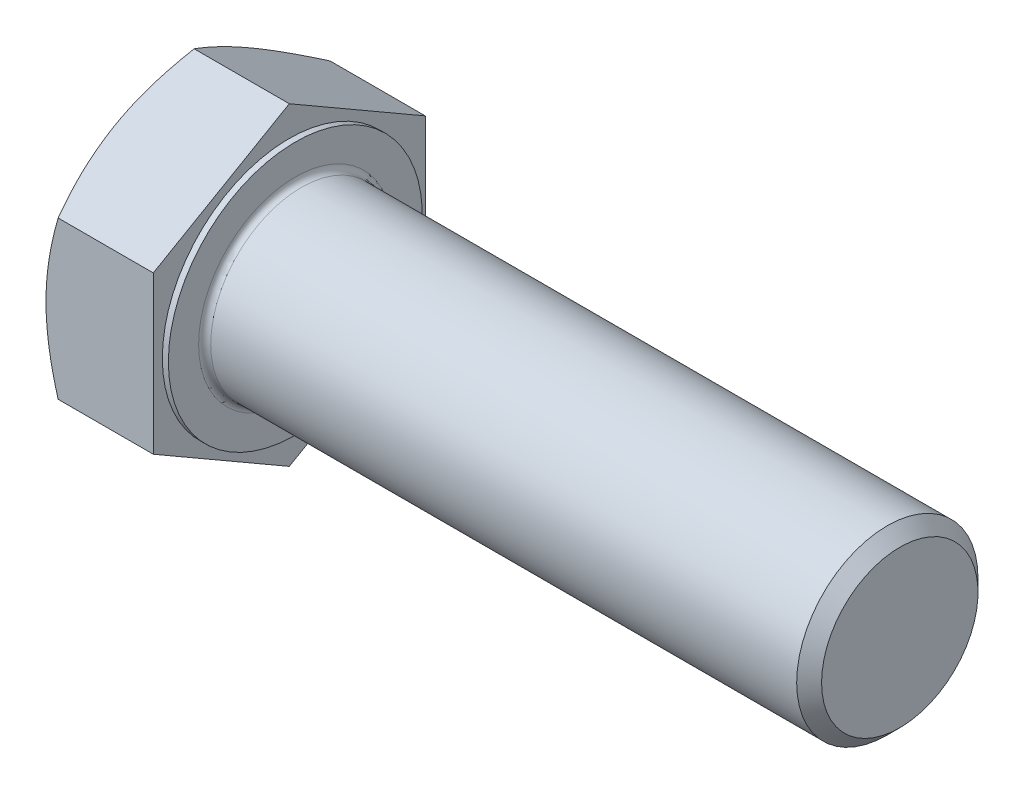
SolidWorks part; units mm, degrees
ref_plane "Front Plane" through (0, 0, 0) normal (0, 0, 1) x (1, 0, 0)
ref_plane "Top Plane" through (0, 0, 0) normal (0, 1, 0) x (1, 0, 0)
ref_plane "Right Plane" through (0, 0, 0) normal (1, 0, 0) x (0, 0, -1)
sketch "BaseHeadSke" plane through (0, 0, 0) normal (1, 0, 0) x (0, 0, -1)
  line L1 (18, 10.3923) -> (0, 20.7846)
  line L2 (0, 20.7846) -> (-18, 10.3923)
  line L3 (-18, 10.3923) -> (-18, -10.3923)
  line L4 (-18, -10.3923) -> (0, -20.7846)
  line L5 (0, -20.7846) -> (18, -10.3923)
  line L6 (18, -10.3923) -> (18, 10.3923)
  circle A0 centre (0, 0) radius 18 construction
extrude "BaseHead" add sketch "BaseHeadSke" along normal blind 15
sketch "BodySke" plane through (0, 0, 0) normal (0, 0, 1) x (1, 0, 0)
  line L0 (0, 0) -> (95, 0)
  line L1 (95, 0) -> (95, 10.352)
  line L2 (95, 10.352) -> (93.352, 12)
  line L3 (93.352, 12) -> (0, 12)
  line L4 (0, 12) -> (0, 0)
  line L5 (15, 10.3923) -> (15, -10.3923) construction
  line L6 (0, 0) -> (159.3976, 0) construction
  line L7 (15, -84.3176) -> (15, 77.7215) construction
  line L8 (92, -21.5941) -> (92, 39.2994) construction
  dimension "Thread_length" = 80
  dimension "Advance" = 3
revolve "BaseBody" add sketch "BodySke" angle 360 about L6
cosmetic thread "ThreadCosmetic" [suppressed] parameters "Thread_length"=80, "Thread_minor"=20.704
sketch "HeadChamferSke" plane through (0, 0, 0) normal (0, 0, 1) x (1, 0, 0)
  line L0 (1.6077, 20.7846) -> (0, 20.7846)
  line L1 (0, 20.7846) -> (0, 18)
  line L2 (0, 18) -> (1.6077, 20.7846)
  line L3 (0, 0) -> (120.9185, 0) construction
  dimension "D1" = 30
revolve "HeadChamfer" cut sketch "HeadChamferSke" angle 360 about L3
sketch "BearingFaceSke" plane through (0, 0, 0) normal (0, 0, 1) x (1, 0, 0)
  line L0 (0, 0) -> (129.6443, 0) construction
  line L1 (14.2, 20.7846) -> (15, 20.7846)
  line L2 (14.2, 20.7846) -> (14.2, 16.805)
  line L3 (14.2, 16.805) -> (15, 16.805)
  line L4 (15, 20.7846) -> (15, 16.805)
  dimension "Bearing_height" = 0.8
  dimension "Dw" = 33.61
revolve "BearingFace" cut sketch "BearingFaceSke" angle 360 about L0
fillet "Fillet" radius 0.8 1 edges at (15, 0, 12)
sketch "ThdSchSke" plane through (0, 0, 0) normal (0, 0, 1) x (1, 0, 0)
  line L0 (91.0485, 13.9029) -> (91.0485, 12)
  line L1 (91.0485, 12) -> (92, 10.352)
  line L2 (92, 10.352) -> (92.9515, 12)
  line L3 (92.9515, 12) -> (92.9515, 13.9029)
  line L4 (92.9515, 13.9029) -> (91.0485, 13.9029)
  line L6 (0, 0) -> (141.9934, 0) construction
  line L7 (95, -10.352) -> (95, 10.352) construction
  dimension "D2" = 20.704
  dimension "D3" = 24
  dimension "Advance" = 3
revolve "ThreadSchematic" [suppressed] cut sketch "ThdSchSke" angle 360 about L6
pattern_linear "ThdSchPat" [suppressed] count 25 spacing 3 along (-1, 0, 0) of bodies 107
equation "\"Thread_minor@ThreadCosmetic\" = \"Minor_dia@BodySke\""
equation "\"Thread_length@ThreadCosmetic\" = \"Thread_length@BodySke\""
equation "\"Head_chamfer@HeadChamferSke\" = \"Width_flats@BaseHeadSke\""
equation "\"D2@ThdSchSke\" = \"Minor_dia@BodySke\""
equation "\"D3@ThdSchSke\" = \"Diameter@BodySke\""
equation "\"Advance@ThdSchSke\" = \"Advance@BodySke\""
equation "\"D3@ThdSchPat\" = \"Advance@BodySke\""
equation "\"D1@ThdSchPat\" =  int( \"Thread_length@BodySke\"/\"Advance@BodySke\" )-1"
